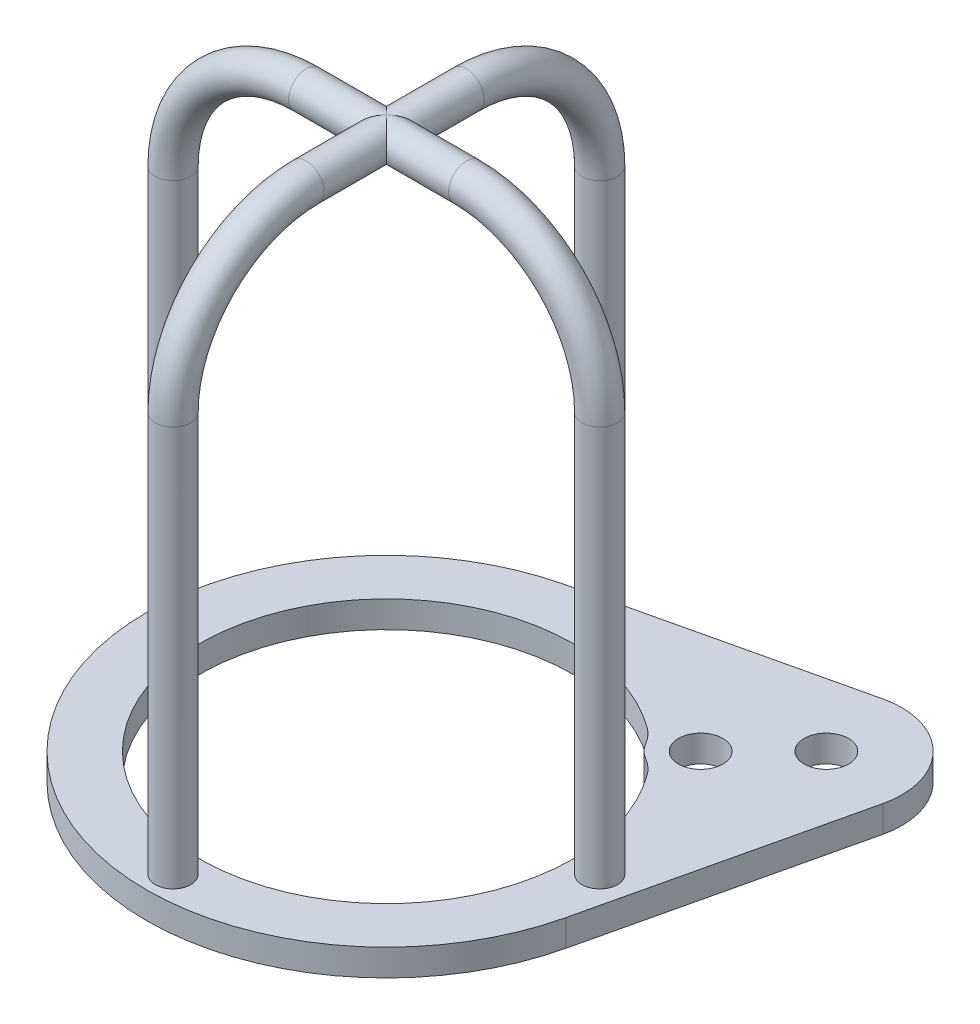
SolidWorks part; units mm, degrees
ref_plane "Plan de face" through (0, 0, 0) normal (0, 0, 1) x (1, 0, 0)
ref_plane "Plan de dessus" through (0, 0, 0) normal (0, 1, 0) x (1, 0, 0)
ref_plane "Plan de droite" through (0, 0, 0) normal (1, 0, 0) x (0, 0, -1)
sketch "Esquisse1" plane through (0, 0, 0) normal (0, 0, 1) x (1, 0, 0)
  line L0 (0, 60) -> (9, 60)
  line L1 (24, 45) -> (24, 0)
  line L2 (0, 0) -> (0, 60) construction
  line L3 (0, 0) -> (24, 0) construction
  arc A0 (24, 45) -> (9, 60) centre (9, 45) ccw
  dimension "D1" = 15
  dimension "D2" = 24
  dimension "D3" = 60
sketch "Esquisse2" plane through (0, 0, 0) normal (0, 1, 0) x (1, 0, 0)
  line L0 (9, 0) -> (24, 0) construction
  line L1 (0, 0) -> (24, 0) construction
  circle A0 centre (24, 0) radius 2
  dimension "D1" = 4
  dimension "D2" = 24
sweep "Balayage1" add profiles "Esquisse2" path "Esquisse1"
sketch "Esquisse3" plane through (0, 0, 0) normal (0, 0, 1) x (1, 0, 0)
  line L0 (0, 0) -> (0, 60) construction
  line L1 (0, 62) -> (0, 58) construction
pattern_circular "Répétition circulaire1" count 4 over 360 about axis through (0, 0, 0) along (0, 1, 0) of "Balayage1" reverse direction yes
sketch "Esquisse4" plane through (0, 0, 0) normal (0, -1, 0) x (1, 0, 0)
  line L0 (0, 0) -> (33.2746, -33.2746) construction
  line L1 (0, 0) -> (0, -27) construction
  line L2 (26.2983, 6.1155) -> (33.0278, -22.8235)
  line L3 (22.8235, -33.0278) -> (-6.1155, -26.2983)
  circle A0 centre (0, 0) radius 21 construction
  circle A1 centre (0, 0) radius 27 construction
  circle A2 centre (17.6777, -17.6777) radius 2.5
  circle A3 centre (24.7487, -24.7487) radius 2.5
  arc A4 (33.0278, -22.8235) -> (22.8235, -33.0278) centre (24.7487, -24.7487) cw
  arc A5 (13.4545, -16.1238) -> (16.1238, -13.4545) centre (17.6777, -17.6777) cw
  arc A6 (16.1238, -13.4545) -> (13.4545, -16.1238) centre (0, 0) ccw
  arc A7 (26.2983, 6.1155) -> (-6.1155, -26.2983) centre (0, 0) ccw
  dimension "D1" = 42
  dimension "D2" = 6
  dimension "D3" = 45
  dimension "D6" = 5
  dimension "D7" = 6
  dimension "D8" = 2
  dimension "D4" = 25
  dimension "D5" = 10
extrude "Boss.-Extru.1" add sketch "Esquisse4" along normal blind 3
fillet "Congé1" radius 5 2 edges at (16.1238, -1.5, -13.4545) (13.4545, -1.5, -16.1238)
